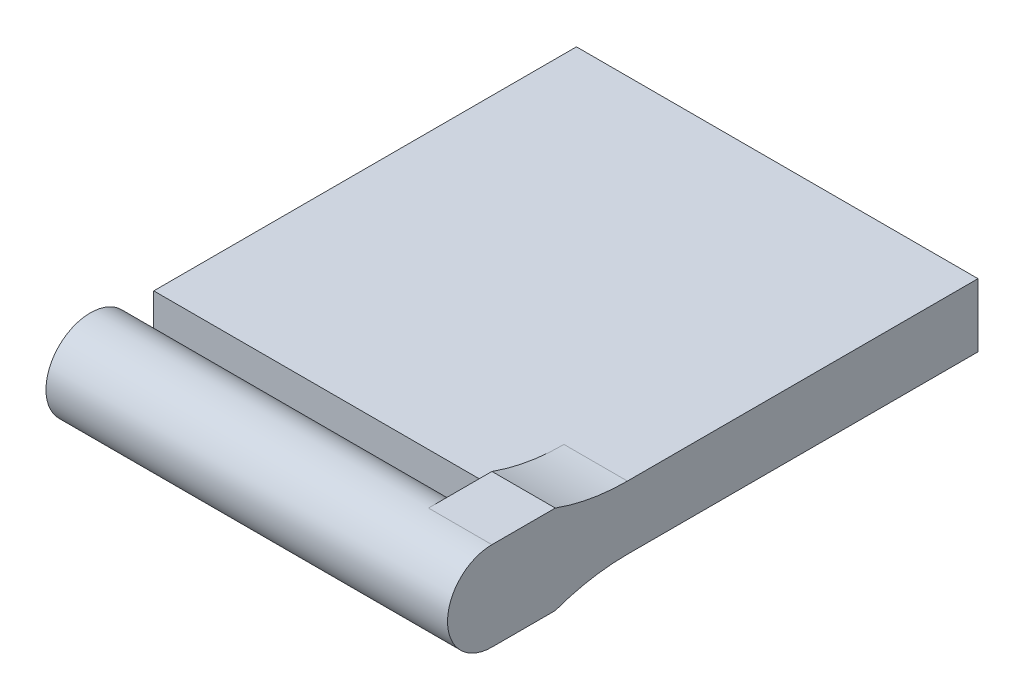
SolidWorks part; units mm, degrees
ref_plane "Front Plane" through (0, 0, 0) normal (0, 0, 1) x (1, 0, 0)
ref_plane "Top Plane" through (0, 0, 0) normal (0, 1, 0) x (1, 0, 0)
ref_plane "Right Plane" through (0, 0, 0) normal (1, 0, 0) x (0, 0, -1)
sketch "Sketch2" plane through (0, 0, 0) normal (1, 0, 0) x (0, 0, -1)
  circle A0 centre (0, 0) radius 2.1
  dimension "D1" = 4.2
extrude "Boss-Extrude1" add sketch "Sketch2" along normal blind 16
sketch "Sketch3" plane through (16, 0, 0) normal (1, 0, 0) x (0, 0, -1)
  line L0 (0, 2.1) -> (3, 2.1)
  line L1 (3, 2.1) -> (3, -2.1)
  line L2 (3, -2.1) -> (0, -2.1)
  circle A0 centre (0, 0) radius 2.1 construction
  circle A1 centre (0, 0) radius 2.1
  circle M4 centre (0, 0) radius 2.1
  dimension "D1" = 3
extrude "Boss-Extrude2" add sketch "Sketch3" along normal blind 3 contours M4 | L2 L1 L0 M4 region at (16, 0, -2.2433) region at (16, 0, 0)
sketch "Sketch4" plane through (19, 0, 0) normal (1, 0, 0) x (0, 0, -1)
  line L0 (3, 2.1) -> (3, -2.1) construction
  line L1 (3, 1.5) -> (23, 1.5)
  line L2 (3, 1.5) -> (3, -1.5)
  line L3 (3, -1.5) -> (23, -1.5)
  line L4 (23, 1.5) -> (23, -1.5)
  point P6 (3, 0)
  dimension "D1" = 3
  dimension "D2" = 20
extrude "Boss-Extrude3" add sketch "Sketch4" against normal up to surface (19 mm away) up to face at (0, 0, -2.1)
fillet "Fillet1" radius 10 2 edges at (17.5, -1.5, -3) (17.5, 1.5, -3)
